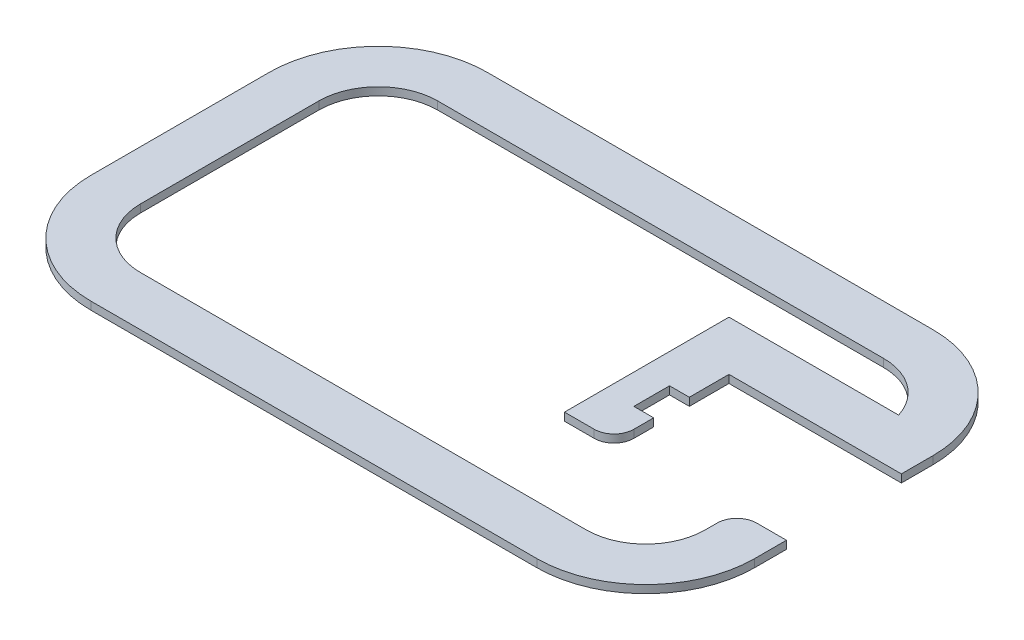
SolidWorks part; units mm, degrees
ref_plane "Front Plane" through (0, 0, 0) normal (0, 0, 1) x (1, 0, 0)
ref_plane "Top Plane" through (0, 0, 0) normal (0, 1, 0) x (1, 0, 0)
ref_plane "Right Plane" through (0, 0, 0) normal (1, 0, 0) x (0, 0, -1)
sketch "Sketch1" plane through (0, 0, 0) normal (0, 1, 0) x (1, 0, 0)
  line L0 (335, 145) -> (335, 129)
  line L1 (55, 0) -> (280, 0)
  line L2 (0, 55) -> (0, 145)
  line L3 (55, 200) -> (280, 200)
  line L4 (335, 55) -> (335, 71)
  line L5 (335, 129) -> (248, 129)
  line L6 (248, 129) -> (248, 109)
  line L7 (248, 109) -> (238, 109)
  line L8 (248, 91) -> (248, 81)
  line L9 (223, 91) -> (223, 71)
  line L10 (238, 109) -> (238, 91)
  line L11 (223, 154) -> (223, 109)
  line L12 (308.6182, 154) -> (223, 154)
  line L13 (308.6182, 154) -> (308.6182, 154)
  line L14 (55, 175) -> (280, 175)
  line L15 (25, 55) -> (25, 145)
  line L16 (55, 25) -> (280, 25)
  line L17 (310, 55) -> (310, 61)
  line L18 (248, 109) -> (248, 91) construction
  line L19 (223, 109) -> (223, 91) construction
  line L20 (238, 91) -> (248, 91)
  line L21 (223, 109) -> (223, 91)
  line L22 (223, 71) -> (238, 71)
  line L23 (320, 71) -> (335, 71)
  line L24 (248, 91) -> (248, 71) construction
  line L25 (310, 55) -> (310, 71) construction
  arc A0 (55, 0) -> (0, 55) centre (55, 55) cw
  arc A1 (280, 0) -> (335, 55) centre (280, 55) ccw
  arc A2 (280, 200) -> (335, 145) centre (280, 145) cw
  arc A3 (0, 145) -> (55, 200) centre (55, 145) cw
  arc A4 (280, 175) -> (308.6182, 154) centre (280, 145) cw
  arc A5 (25, 145) -> (55, 175) centre (55, 145) cw
  arc A6 (55, 25) -> (25, 55) centre (55, 55) cw
  arc A7 (280, 25) -> (310, 55) centre (280, 55) ccw
  arc A8 (248, 81) -> (238, 71) centre (238, 81) cw
  arc A9 (310, 61) -> (320, 71) centre (320, 61) cw
  point P7 (0, 0)
  point P15 (0, 200)
  point P47 (248, 71)
  dimension "D3" = 55
  dimension "D12" = 10
  dimension "D13" = 10
  dimension "D1" = 335
  dimension "D2" = 200
  dimension "D4" = 87
  dimension "D5" = 20
  dimension "D6" = 18
  dimension "D7" = 20
  dimension "D8" = 25
  dimension "D9" = 10
  dimension "D10" = 16
  dimension "D11" = 16
extrude "Boss-Extrude1" add sketch "Sketch1" along normal blind 4
